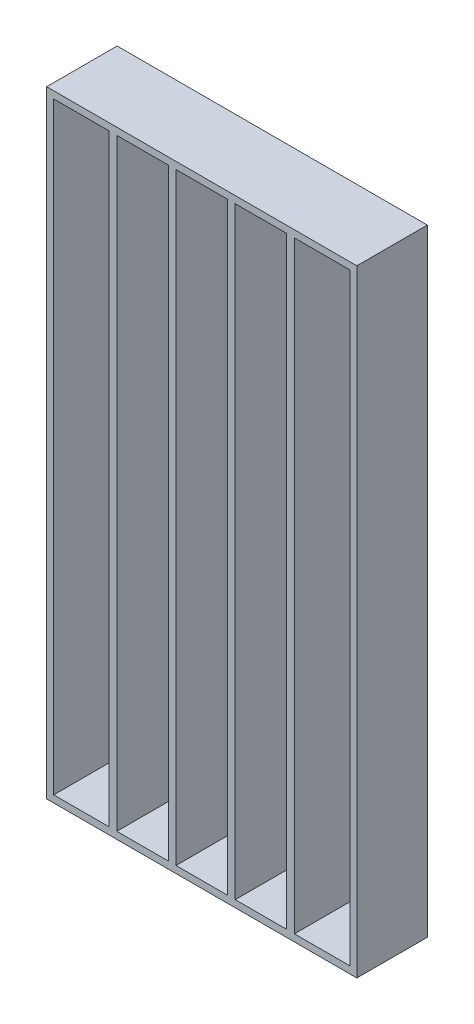
SolidWorks part; units mm, degrees
ref_plane "Front Plane" through (0, 0, 0) normal (0, 0, 1) x (1, 0, 0)
ref_plane "Top Plane" through (0, 0, 0) normal (0, 1, 0) x (1, 0, 0)
ref_plane "Right Plane" through (0, 0, 0) normal (1, 0, 0) x (0, 0, -1)
sketch "Sketch1" plane through (0, 0, 0) normal (0, 0, 1) x (1, 0, 0)
  line L1 (-44, -87.5) -> (44, -87.5)
  line L2 (-44, -87.5) -> (-44, 87.5)
  line L3 (-44, 87.5) -> (44, 87.5)
  line L4 (44, -87.5) -> (44, 87.5)
  line L5 (-44, -87.5) -> (44, 87.5) construction
  line L6 (-44, 87.5) -> (44, -87.5) construction
  point P0 (0, 0)
  dimension "D1" = 88
  dimension "D2" = 175
extrude "Boss-Extrude1" add sketch "Sketch1" along normal blind 2
sketch "Sketch2" plane through (0, 0, 2) normal (0, 0, 1) x (1, 0, 0)
  line L4 (44, -87.5) -> (44, 87.5)
  line L5 (44, 87.5) -> (-44, 87.5)
  line L6 (-44, 87.5) -> (-44, -87.5)
  line L7 (-44, -87.5) -> (44, -87.5)
  line L8 (44, -87.5) -> (44, 87.5)
  line L9 (44, 87.5) -> (-44, 87.5)
  line L10 (-44, 87.5) -> (-44, -87.5)
  line L11 (-44, -87.5) -> (44, -87.5)
  dimension "D1" = 0
extrude "Extrude-Thin1" add sketch "Sketch2" along normal blind 18 thin thin type one direction reverse wall 2
sketch "Sketch3" plane through (0, 0, 2) normal (0, 0, 1) x (1, 0, 0)
  line L0 (-25.2, 85.5) -> (-25.2, -85.5)
  line L1 (42, 85.5) -> (-42, 85.5) construction
  line L2 (-42, -85.5) -> (42, -85.5) construction
  line L3 (-8.4, 85.5) -> (-8.4, -85.5)
  line L4 (42, 85.5) -> (-42, 85.5) construction
  line L5 (25.2, 85.5) -> (25.2, -85.5)
  line L6 (8.4, 85.5) -> (8.4, -85.5)
  line L7 (-42, -85.5) -> (42, -85.5) construction
  line L8 (-42, 85.5) -> (-42, -85.5) construction
  line L9 (42, -85.5) -> (42, 85.5) construction
  dimension "D1" = 16.8
  dimension "D2" = 16.8
  dimension "D3" = 16.8
  dimension "D4" = 16.8
  dimension "D5" = 16.8
extrude "Extrude-Thin2" add sketch "Sketch3" along normal blind 18 thin thin type mid plane wall 2.2
